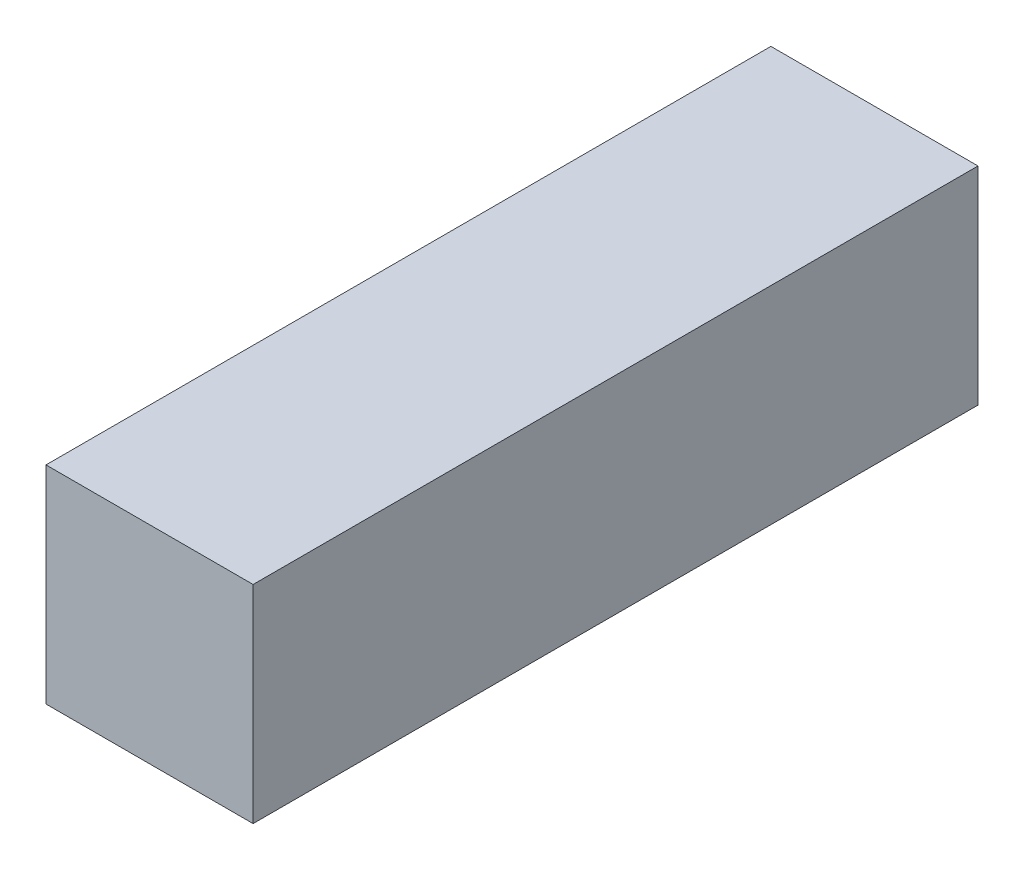
SolidWorks part; units mm, degrees
ref_plane "Front Plane" through (0, 0, 0) normal (0, 0, 1) x (1, 0, 0)
ref_plane "Top Plane" through (0, 0, 0) normal (0, 1, 0) x (1, 0, 0)
ref_plane "Right Plane" through (0, 0, 0) normal (1, 0, 0) x (0, 0, -1)
sketch "Sketch1" plane through (0, 0, 0) normal (0, 0, 1) x (1, 0, 0)
  line L3 (2, -2) -> (-2, -2)
  line L4 (2, -2) -> (2, 2)
  line L5 (2, 2) -> (-2, 2)
  line L6 (-2, -2) -> (-2, 2)
  line L7 (2, -2) -> (-2, 2) construction
  line L8 (2, 2) -> (-2, -2) construction
  point P0 (0, 0)
  dimension "Width" = 4
  dimension "Height" = 4
sketch "Sketch2" plane through (0, 0, 0) normal (1, 0, 0) x (0, 0, -1)
  line L0 (-4.2, 0) -> (4.2, 0) construction
  line L2 (7, -2) -> (-7, -2)
  line L3 (7, -2) -> (7, 2)
  line L4 (7, 2) -> (-7, 2)
  line L5 (-7, -2) -> (-7, 2)
  line L6 (7, -2) -> (-7, 2) construction
  line L7 (7, 2) -> (-7, -2) construction
  point P0 (0, 0)
  point P4 (0, 0)
  point P11 (4.2, 0)
  point P12 (-4.2, 0)
  point P14 (-2.88, 0)
  dimension "Length" = 14
  dimension "D1" = 8.4
  dimension "D3" = 1.32
sketch "Sketch3" plane through (0, 0, 0) normal (0, 0, 1) x (1, 0, 0)
  line L0 (2, -2) -> (2, 2) construction
  line L5 (2, -2) -> (-2, -2) construction
  line L6 (-2, -2) -> (-2, 2) construction
  line L7 (2, 2) -> (-2, 2) construction
  line L8 (2, -2) -> (2, 2)
  line L9 (2, -2) -> (-2, -2)
  line L10 (-2, -2) -> (-2, 2)
  line L11 (2, 2) -> (-2, 2)
extrude "Boss-Extrude1" add sketch "Sketch3" along normal up to vertex (7 mm away) and the other way up to vertex (7 mm away) up to point (0, 2, 7) other way up to point (0, 2, -7)
ref_plane "Contact Plane 1" through (0, 0, 7) normal (0, 0, 1) x (1, 0, 0)
ref_plane "Contact Plane 2" through (0, 0, -7) normal (0, 0, 1) x (1, 0, 0)
ref_axis "Center Axis 1" through (0, 0, -5.5) along (0, 0, 1)
equation "\"D1@Sketch2\"=\"Length@Sketch2\"*.6"
equation "\"D3@Sketch2\"=\"Width@Sketch1\"*.33"
